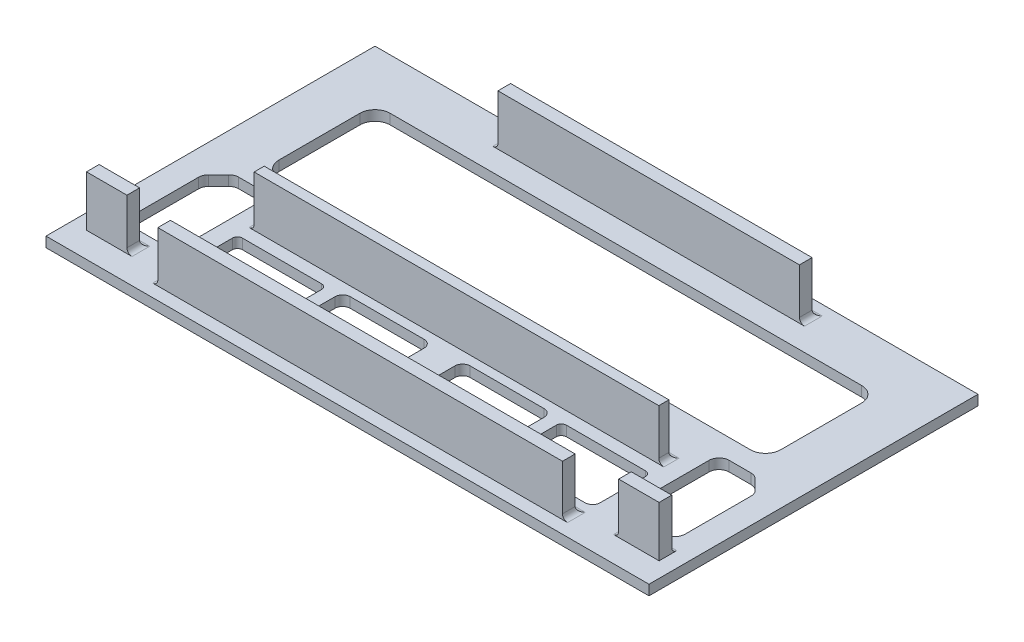
SolidWorks part; units mm, degrees
ref_plane "Front Plane" through (0, 0, 0) normal (0, 0, 1) x (1, 0, 0)
ref_plane "Top Plane" through (0, 0, 0) normal (0, 1, 0) x (1, 0, 0)
ref_plane "Right Plane" through (0, 0, 0) normal (1, 0, 0) x (0, 0, -1)
sketch "Sketch1" plane through (0, 0, 0) normal (0, 1, 0) x (1, 0, 0)
  line L1 (-59.6, -32.52) -> (59.6, -32.52)
  line L2 (-59.6, -32.52) -> (-59.6, 32.52)
  line L3 (-59.6, 32.52) -> (59.6, 32.52)
  line L4 (59.6, -32.52) -> (59.6, 32.52)
  line L5 (-59.6, -32.52) -> (59.6, 32.52) construction
  line L6 (-59.6, 32.52) -> (59.6, -32.52) construction
  point P0 (0, 0)
  dimension "D1" = 119.2
  dimension "D2" = 65.04
extrude "Boss-Extrude1" add sketch "Sketch1" along normal blind 2
ref_plane "Plane1" through (0, 0, 0) normal (-1, 0, 0) x (0, 0, 1)
sketch "Sketch2" plane through (0, 2, 0) normal (0, 1, 0) x (1, 0, 0)
  line L0 (-29.8, 29.52) -> (29.8, 29.52)
  line L1 (59.6, 32.52) -> (-59.6, 32.52) construction
  line L2 (59.6, -32.52) -> (59.6, 32.52) construction
  line L3 (59.6, -27.02) -> (59.6, -29.52)
  line L4 (29.8, 27.02) -> (-29.8, 27.02)
  line L5 (40, -8.98) -> (-40, -8.98)
  line L7 (-29.8, 29.52) -> (-29.8, 27.02)
  line L8 (29.8, 29.52) -> (29.8, 27.02)
  line L9 (-40, -8.98) -> (-40, -10.98)
  line L10 (-40, -10.98) -> (40, -10.98)
  line L11 (40, -10.98) -> (40, -8.98)
  dimension "D1" = 3
  dimension "D2" = 2.5
  dimension "D3" = 43.5
  dimension "D4" = 29.8
  dimension "D5" = 2
  dimension "D9" = 80
extrude "Boss-Extrude2" add sketch "Sketch2" along normal blind 10 contours L10 L11 L5 L9 | L8 L0 L7 L4 region at (0, 2, -28.27) region at (0, 2, 9.98)
fillet "Fillet1" radius 1 6 edges at (-29.8, 2, -28.27) (29.8, 2, -28.27) (0, 2, -29.52) (-40, 2, 9.98) (40, 2, 9.98) (0, 2, 8.98)
sketch "Sketch4" plane through (0, 2, 0) normal (0, 1, 0) x (1, 0, 0)
  line L0 (40, -30.02) -> (-40, -30.02)
  line L1 (-40, -30.02) -> (-40, -27.52)
  line L2 (-40, -27.52) -> (40, -27.52)
  line L3 (40, -27.52) -> (40, -30.02)
  line L4 (-59.6, -32.52) -> (59.6, -32.52) construction
  line L5 (0, 1.1) -> (0, -1.1) construction
  line L6 (48.6, -27.52) -> (56.6, -27.52)
  line L7 (56.6, -27.52) -> (56.6, -25.02)
  line L8 (56.6, -25.02) -> (48.6, -25.02)
  line L9 (48.6, -25.02) -> (48.6, -27.52)
  line L15 (59.6, -32.52) -> (59.6, 32.52) construction
  point P6 (0, -27.52)
  point P15 (52.6, -27.52)
  dimension "D1" = 2.5
  dimension "D2" = 2.5
  dimension "D3" = 80
  dimension "D4" = 2.5
  dimension "D6" = 3
  dimension "D7" = 8
extrude "Boss-Extrude3" add sketch "Sketch4" along normal blind 10
fillet "Fillet2" radius 1 5 edges at (-40, 2, 28.77) (48.6, 2, 26.27) (52.6, 2, 25.02) (40, 2, 28.77) (0, 2, 27.52)
mirror "Mirror1" about plane through (0, 0, 0) normal (-1, 0, 0) of "Boss-Extrude3"
fillet "Fillet3" radius 1 2 edges at (-52.6, 2, 25.02) (-48.6, 2, 26.27)
sketch "Sketch5" plane through (0, 2, 0) normal (0, 1, 0) x (1, 0, 0)
  line L0 (46.6, 22.52) -> (6.3115, 22.52)
  line L1 (6.3115, 22.52) -> (-46.6, 22.52)
  line L2 (-49.6, 19.52) -> (-49.6, 3.52)
  line L3 (-46.6, 0.52) -> (46.6, 0.52)
  line L4 (49.6, 3.52) -> (49.6, 19.52)
  line L5 (59.6, 32.52) -> (-59.6, 32.52) construction
  line L6 (59.6, -32.52) -> (59.6, 32.52) construction
  line L7 (-59.6, 32.52) -> (-59.6, -32.52) construction
  arc A0 (-49.6, 3.52) -> (-46.6, 0.52) centre (-46.6, 3.52) ccw
  arc A1 (-46.6, 22.52) -> (-49.6, 19.52) centre (-46.6, 19.52) ccw
  arc A2 (46.6, 22.52) -> (49.6, 19.52) centre (46.6, 19.52) cw
  arc A3 (46.6, 0.52) -> (49.6, 3.52) centre (46.6, 3.52) ccw
  dimension "D5" = 3
  dimension "D1" = 10
  dimension "D2" = 10
  dimension "D3" = 10
  dimension "D4" = 22
extrude "Cut-Extrude2" cut sketch "Sketch5" against normal blind 10
sketch "Sketch6" plane through (0, 2, 0) normal (0, 1, 0) x (1, 0, 0)
  line L3 (54.0142, -5.9408) -> (52.0453, -3.9719)
  line L4 (50.6311, -3.3862) -> (46.3278, -3.3862)
  line L5 (54.6, -7.3551) -> (54.6, -20.3979)
  line L6 (52.6, -22.3979) -> (46.3278, -22.3979)
  line L7 (44.3278, -20.3979) -> (44.3278, -5.3862)
  line L10 (39.8278, -13.4493) -> (24.2108, -13.4493)
  line L16 (4.044, -24.8936) -> (19.6609, -24.8936)
  line L17 (40.8278, -14.4493) -> (40.8278, -23.3936)
  line L18 (39.3278, -24.8936) -> (24.7108, -24.8936)
  line L19 (23.2108, -23.3936) -> (23.2108, -14.4493)
  line L21 (20.6609, -23.8936) -> (20.6609, -14.3214)
  line L22 (19.1609, -12.8214) -> (4.544, -12.8214)
  line L23 (3.044, -14.3214) -> (3.044, -23.8936)
  line L25 (59.6, -32.52) -> (59.6, 32.52) construction
  line L26 (0, -47.4967) -> (0, 52.968) construction
  line L29 (-4.044, -24.8936) -> (-19.6609, -24.8936)
  line L31 (-3.044, -14.3214) -> (-3.044, -23.8936)
  line L33 (-19.1609, -12.8214) -> (-4.544, -12.8214)
  line L34 (-20.6609, -23.8936) -> (-20.6609, -14.3214)
  line L37 (-39.3278, -24.8936) -> (-24.7108, -24.8936)
  line L39 (-39.8278, -13.4493) -> (-24.2108, -13.4493)
  line L40 (-23.2108, -14.4493) -> (-23.2108, -23.3936)
  line L42 (-40.8278, -23.3936) -> (-40.8278, -14.4493)
  line L43 (-44.3278, -5.3862) -> (-44.3278, -20.3979)
  line L44 (-50.6311, -3.3862) -> (-46.3278, -3.3862)
  line L45 (-54.0142, -5.9408) -> (-52.0453, -3.9719)
  line L46 (-54.6, -20.3979) -> (-54.6, -7.3551)
  line L51 (-52.6, -22.3979) -> (-46.3278, -22.3979)
  arc A1 (44.3278, -5.3862) -> (46.3278, -3.3862) centre (46.3278, -5.3862) cw
  arc A2 (52.0453, -3.9719) -> (50.6311, -3.3862) centre (50.6311, -5.3862) ccw
  arc A3 (54.6, -7.3551) -> (54.0142, -5.9408) centre (52.6, -7.3551) ccw
  arc A5 (46.3278, -22.3979) -> (44.3278, -20.3979) centre (46.3278, -20.3979) cw
  arc A8 (54.6, -20.3979) -> (52.6, -22.3979) centre (52.6, -20.3979) cw
  arc A10 (4.544, -12.8214) -> (3.044, -14.3214) centre (4.544, -14.3214) ccw
  arc A11 (20.6609, -14.3214) -> (19.1609, -12.8214) centre (19.1609, -14.3214) ccw
  arc A15 (24.7108, -24.8936) -> (23.2108, -23.3936) centre (24.7108, -23.3936) cw
  arc A16 (40.8278, -23.3936) -> (39.3278, -24.8936) centre (39.3278, -23.3936) cw
  arc A18 (3.044, -23.8936) -> (4.044, -24.8936) centre (4.044, -23.8936) ccw
  arc A19 (20.6609, -23.8936) -> (19.6609, -24.8936) centre (19.6609, -23.8936) cw
  arc A21 (40.8278, -14.4493) -> (39.8278, -13.4493) centre (39.8278, -14.4493) ccw
  arc A23 (24.2108, -13.4493) -> (23.2108, -14.4493) centre (24.2108, -14.4493) ccw
  arc A26 (-3.044, -23.8936) -> (-4.044, -24.8936) centre (-4.044, -23.8936) cw
  arc A27 (-20.6609, -23.8936) -> (-19.6609, -24.8936) centre (-19.6609, -23.8936) ccw
  arc A29 (-4.544, -12.8214) -> (-3.044, -14.3214) centre (-4.544, -14.3214) cw
  arc A31 (-20.6609, -14.3214) -> (-19.1609, -12.8214) centre (-19.1609, -14.3214) cw
  arc A35 (-40.8278, -23.3936) -> (-39.3278, -24.8936) centre (-39.3278, -23.3936) ccw
  arc A36 (-24.7108, -24.8936) -> (-23.2108, -23.3936) centre (-24.7108, -23.3936) ccw
  arc A37 (-24.2108, -13.4493) -> (-23.2108, -14.4493) centre (-24.2108, -14.4493) cw
  arc A40 (-40.8278, -14.4493) -> (-39.8278, -13.4493) centre (-39.8278, -14.4493) cw
  arc A41 (-44.3278, -5.3862) -> (-46.3278, -3.3862) centre (-46.3278, -5.3862) ccw
  arc A43 (-52.0453, -3.9719) -> (-50.6311, -3.3862) centre (-50.6311, -5.3862) cw
  arc A44 (-54.6, -7.3551) -> (-54.0142, -5.9408) centre (-52.6, -7.3551) cw
  arc A46 (-46.3278, -22.3979) -> (-44.3278, -20.3979) centre (-46.3278, -20.3979) ccw
  arc A49 (-54.6, -20.3979) -> (-52.6, -22.3979) centre (-52.6, -20.3979) ccw
  point P66 (3.044, -22.0111)
  point P71 (20.6609, -24.8936)
  point P74 (20.6609, -22.0111)
  dimension "D1" = 5
  dimension "D8" = 3.5
extrude "Cut-Extrude3" cut sketch "Sketch6" against normal blind 10
